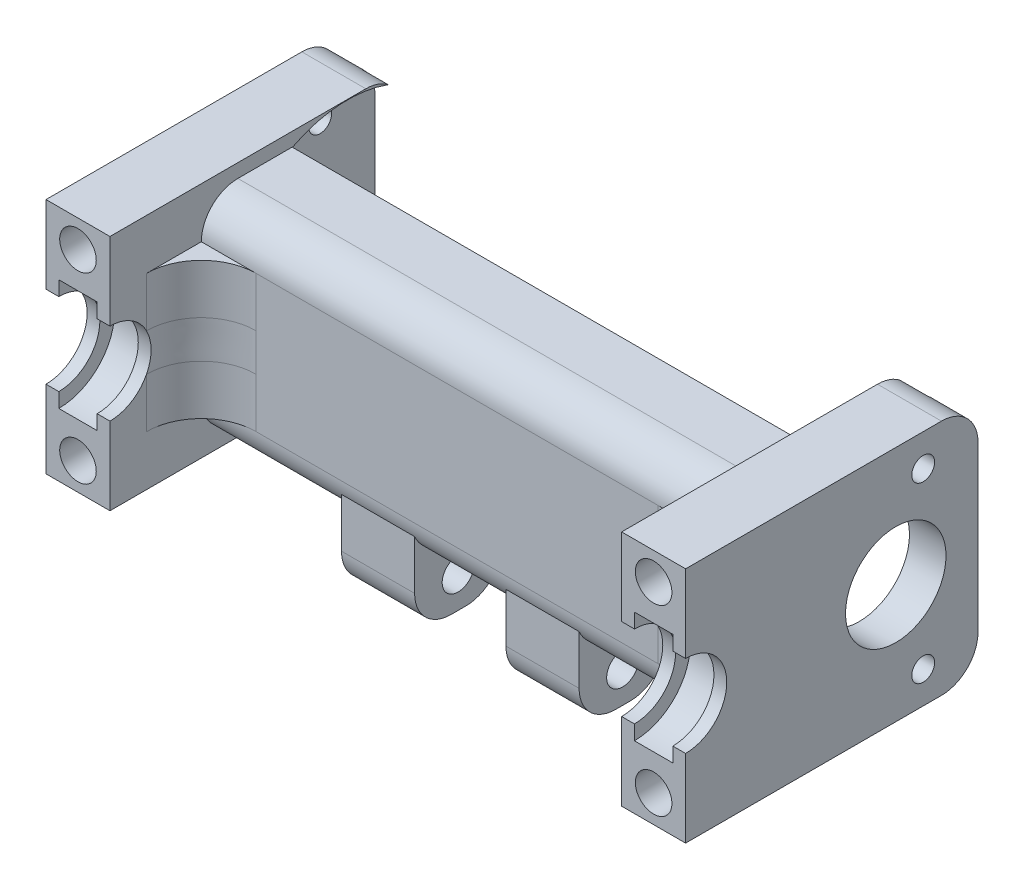
SolidWorks part; units mm, degrees
ref_plane "Front Plane" through (0, 0, 0) normal (0, 0, 1) x (1, 0, 0)
ref_plane "Top Plane" through (0, 0, 0) normal (0, 1, 0) x (1, 0, 0)
ref_plane "Right Plane" through (0, 0, 0) normal (1, 0, 0) x (0, 0, -1)
sketch "Sketch1" plane through (0, 0, 0) normal (0, 0, 1) x (1, 0, 0)
  line L1 (-35, 7.5) -> (35, 7.5)
  line L2 (-35, 7.5) -> (-35, -7.5)
  line L3 (-35, -7.5) -> (35, -7.5)
  line L4 (35, 7.5) -> (35, -7.5)
  line L5 (-35, 7.5) -> (35, -7.5) construction
  line L6 (-35, -7.5) -> (35, 7.5) construction
  point P0 (0, 0)
  dimension "D1" = 15
  dimension "D2" = 70
extrude "Boss-Extrude1" add sketch "Sketch1" along normal blind 3
sketch "Sketch2" plane through (0, 0, 3) normal (0, 0, 1) x (1, 0, 0)
  line L0 (-35, -7.5) -> (35, -7.5) construction
  line L1 (-35, 7.5) -> (-28, 7.5)
  line L2 (-35, 7.5) -> (-35, -7.5)
  line L3 (-35, -7.5) -> (-28, -7.5)
  line L4 (-28, 7.5) -> (-28, -7.5)
  line L6 (35, 7.5) -> (28, 7.5)
  line L7 (35, 7.5) -> (35, -7.5)
  line L8 (35, -7.5) -> (28, -7.5)
  line L9 (28, 7.5) -> (28, -7.5)
  dimension "D1" = 7
  dimension "D2" = 7
extrude "Boss-Extrude2" add sketch "Sketch2" along normal blind 10
sketch "Sketch5" plane through (35, 0, 0) normal (1, 0, 0) x (0, 0, -1)
  line L0 (-13, -7.5) -> (-13, 7.5) construction
  circle A0 centre (-13, 0) radius 4.5
  dimension "D1" = 9
extrude "Cut-Extrude1" cut sketch "Sketch5" against normal through all
ref_plane "Plane1" through (31.5, 0, 0) normal (1, 0, 0) x (0, 0, -1)
sketch "Sketch6" plane through (31.5, 0, 0) normal (1, 0, 0) x (0, 0, -1)
  circle A0 centre (-13, 0) radius 6.1
  dimension "D1" = 12.2
extrude "Cut-Extrude4" cut sketch "Sketch6" against normal blind 2.1 and the other way blind 2.1
sketch "Sketch7" plane through (0, 0, 0) normal (0, 0, 1) x (1, 0, 0)
  line L1 (28, 8.1) -> (28, 13)
  line L2 (28, 13) -> (35, 13)
  line L3 (35, 13) -> (35, 8.1)
  line L4 (35, 7.5) -> (28, 7.5) construction
  line L9 (29.4, 6.1) -> (33.6, 6.1)
  line L10 (29.4, 6.1) -> (33.6, 6.1)
  line L11 (33.6, 6.1) -> (33.6, 4.5)
  line L12 (33.6, 4.5) -> (35, 4.5)
  line L13 (35, 4.5) -> (35, 7.5)
  line L14 (35, 7.5) -> (28, 7.5)
  line L15 (28, 7.5) -> (28, 4.5)
  line L16 (33.6, 6.1) -> (33.6, 4.5)
  line L17 (28, 4.5) -> (29.4, 4.5)
  line L20 (33.6, 4.5) -> (35, 4.5)
  line L21 (35, 4.5) -> (35, 8.1)
  line L23 (28, 8.1) -> (28, 4.5)
  line L26 (28, 4.5) -> (29.4, 4.5)
  line L27 (29.4, 4.5) -> (29.4, 6.1)
  line L28 (29.4, 4.5) -> (29.4, 6.1)
  dimension "D2" = 5.5
  dimension "D1" = 0
extrude "Boss-Extrude3" add sketch "Sketch7" along normal blind 13
sketch "Sketch8" plane through (0, 0, 13) normal (0, 0, 1) x (1, 0, 0)
  line L0 (31.5, 13) -> (31.5, 10) construction
  line L1 (35, 13) -> (28, 13) construction
  circle A0 centre (31.5, 10) radius 2
  dimension "D1" = 4
  dimension "D2" = 3
extrude "Cut-Extrude5" cut sketch "Sketch8" against normal through all both and the other way through all
sketch "Sketch9" plane through (0, 0, 3) normal (0, 0, 1) x (1, 0, 0)
  circle A0 centre (-10, -4) radius 1.75
  dimension "D3" = 3.5
  dimension "D1" = 10
  dimension "D2" = 4
extrude "Cut-Extrude6" cut sketch "Sketch9" against normal through all
mirror "Mirror1" about plane through (0, 0, 0) normal (1, 0, 0) of "Cut-Extrude6", "Cut-Extrude5", "Boss-Extrude3", "Cut-Extrude4" second plane through (0, 0, 0) second plane normal (0, 1, 0)
fillet "Fillet1" radius 6 2 edges at (28, 0, 3) (-28, 0, 3)
sketch "Sketch10" plane through (0, 0, 3) normal (0, 0, -1) x (-1, 0, 0)
  line L1 (-28, -11.5) -> (28, -11.5)
  line L2 (-28, -11.5) -> (-28, 11.5)
  line L3 (-28, 11.5) -> (28, 11.5)
  line L4 (28, -11.5) -> (28, 11.5)
  line L5 (-28, -11.5) -> (28, 11.5) construction
  line L6 (-28, 11.5) -> (28, -11.5) construction
  point P0 (0, 0)
  dimension "D1" = 23
  dimension "D2" = 56
extrude "Boss-Extrude4" add sketch "Sketch10" along normal blind 15
fillet "Fillet2" radius 4 2 edges at (0, 11.5, 3) (0, -11.5, 3)
sketch "Sketch11" plane through (28, 0, 0) normal (1, 0, 0) x (0, 0, -1)
  line L0 (0, 0) -> (13, 0) construction
  circle A0 centre (13, 0) radius 13
  dimension "D1" = 26
extrude "Cut-Extrude7" cut sketch "Sketch11" against normal through all
sketch "Sketch12" plane through (0, -11.5, 0) normal (0, -1, 0) x (1, 0, 0)
  line L1 (-5, 2.6586) -> (-13, 2.6586)
  line L2 (-5, 2.6586) -> (-5, -6.9378)
  line L3 (-5, -6.9378) -> (-13, -6.9378)
  line L4 (-13, 2.6586) -> (-13, -6.9378)
  line L5 (-28, -6.9378) -> (28, -6.9378) construction
  dimension "D1" = 5
  dimension "D2" = 8
extrude "Boss-Extrude5" add sketch "Sketch12" along normal blind 7 and the other way up to next
fillet "Fillet3" radius 4 2 edges at (-9, -18.5, -6.9378) (-9, -18.5, 2.6586)
sketch "Sketch13" plane through (-5, 0, 0) normal (1, 0, 0) x (0, 0, -1)
  line L0 (2.1396, -18.5) -> (2.1085, -15) construction
  line L1 (2.9378, -18.5) -> (1.3414, -18.5) construction
  circle A0 centre (2.1085, -15) radius 1.75
  dimension "D1" = 3.5
  dimension "D2" = 3.5
extrude "Cut-Extrude8" cut sketch "Sketch13" against normal through all
sketch "Sketch14" plane through (0, 0, 0) normal (0, 0, -1) x (-1, 0, 0)
  line L0 (35, 13) -> (35, -13) construction
  line L1 (35, 13) -> (28, 13)
  line L2 (35, 13) -> (35, -13)
  line L3 (35, -13) -> (28, -13)
  line L4 (28, 13) -> (28, -13)
  line L5 (28, 0) -> (28, -11.373) construction
  line L6 (28, 0) -> (0, 0) construction
  dimension "D1" = 26
extrude "Boss-Extrude6" add sketch "Sketch14" along normal blind 5
sketch "Sketch15" plane through (0, 0, -5) normal (0, 0, -1) x (-1, 0, 0)
  line L0 (31.5, 0) -> (28, 0) construction
  line L1 (28, -13) -> (35, -13)
  line L2 (28, -13) -> (28, 13)
  line L3 (28, 13) -> (35, 13)
  line L4 (35, -13) -> (35, 13)
  line L5 (28, -13) -> (35, 13) construction
  line L6 (28, 13) -> (35, -13) construction
  line L8 (31.5, 0) -> (31.5, -13) construction
  line L9 (28, -13) -> (35, -13) construction
  line L10 (28, 10.247) -> (28, -10.247) construction
  point P0 (31.5, 0)
  dimension "D1" = 26
extrude "Boss-Extrude7" add sketch "Sketch15" along normal blind 14
fillet "Fillet5" radius 4 2 edges at (-31.5, 13, -19) (-31.5, -13, -19)
sketch "Sketch16" plane through (-35, 0, 0) normal (-1, 0, 0) x (0, 0, 1)
  line L0 (0, -8) -> (0, 8) construction
  line L1 (0, 0) -> (-10, 0) construction
  circle A0 centre (-10, 0) radius 5.5
  dimension "11" = 11
  dimension "D1" = 10
extrude "Cut-Extrude9" cut sketch "Sketch16" against normal through all
mirror "Mirror2" about plane through (0, 0, 0) normal (1, 0, 0) of "Cut-Extrude9", "Fillet5", "Boss-Extrude7", "Boss-Extrude6", "Boss-Extrude5", "Fillet3", "Cut-Extrude8"
sketch "Sketch17" plane through (-35, 0, 0) normal (-1, 0, 0) x (0, 0, 1)
  line L0 (-10, 0) -> (-13, 0) construction
  line L1 (-13, 0) -> (-13, 9.5) construction
  line L2 (-13, 0) -> (-13, -9.5) construction
  circle A0 centre (-13, 9.5) radius 1.25
  circle A1 centre (-13, -9.5) radius 1.25
  dimension "D4" = 2.5
  dimension "D5" = 2.5
  dimension "D1" = 3
  dimension "D2" = 9.5
  dimension "D3" = 9.5
extrude "Cut-Extrude10" cut sketch "Sketch17" against normal through all
sketch "Sketch18" plane through (0, 0, 0) normal (1, 0, 0) x (0, 0, -1)
  line L0 (13, 9.5) -> (13, -9.5) construction
  circle A0 centre (13, 0) radius 12.95
  dimension "D1" = 25.9
extrude "Cut-Extrude14" cut sketch "Sketch18" against normal blind 31 and the other way blind 31
